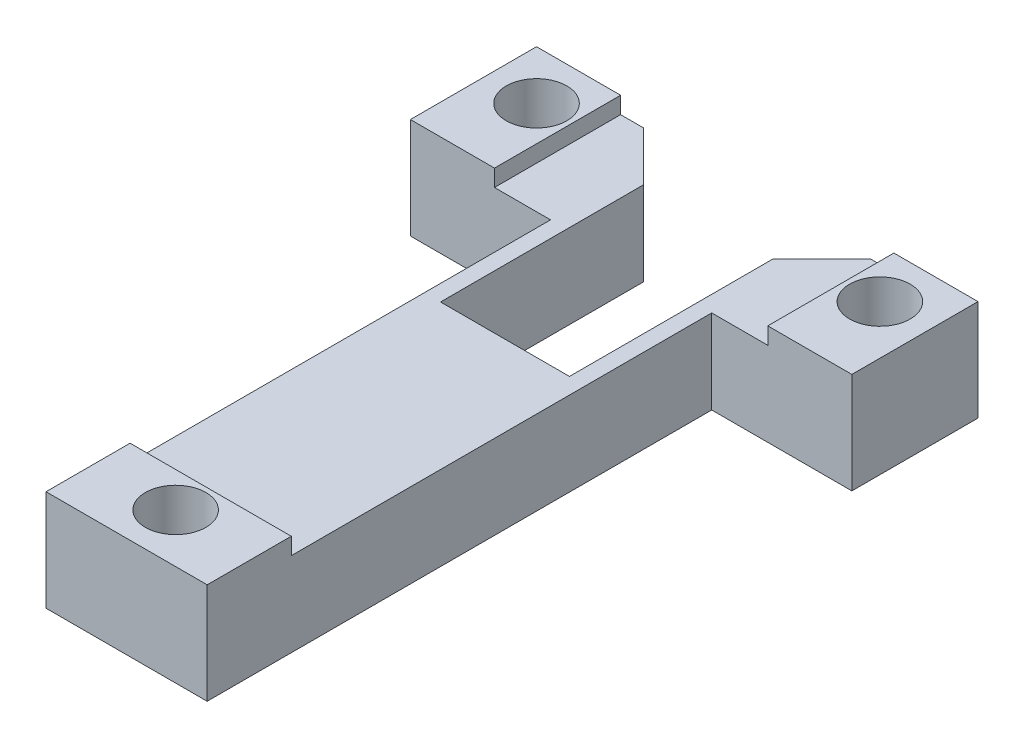
SolidWorks part; units mm, degrees
ref_plane "Front Plane" through (0, 0, 0) normal (0, 0, 1) x (1, 0, 0)
ref_plane "Top Plane" through (0, 0, 0) normal (0, 1, 0) x (1, 0, 0)
ref_plane "Right Plane" through (0, 0, 0) normal (1, 0, 0) x (0, 0, -1)
sketch "Sketch1" plane through (0, 0, 0) normal (0, 1, 0) x (1, 0, 0)
  line L0 (11.5, 45) -> (21.5, 45)
  line L1 (0, 0) -> (11.5, 0)
  line L2 (0, 0) -> (0, 45)
  line L3 (0, 45) -> (11.5, 45)
  line L4 (11.5, 0) -> (11.5, 45)
  line L5 (21.5, 45) -> (21.5, 36)
  line L6 (21.5, 36) -> (11.5, 36)
  line L7 (0, 45) -> (-10, 45)
  line L8 (-10, 45) -> (-10, 36)
  line L9 (-10, 36) -> (0, 36)
  dimension "D3" = 9
  dimension "D1" = 45
  dimension "D2" = 11.5
  dimension "D4" = 10
  dimension "D5" = 10
extrude "Boss-Extrude1" add sketch "Sketch1" along normal blind 6 contours L8 L9 L2 L7 | L6 L5 L0 L4 | L4 L3 L2 L1 region at (16.5, 0, -40.5) region at (-5, 0, -40.5)
sketch "Sketch3" plane through (0, 6, 0) normal (0, 1, 0) x (1, 0, 0)
  line L0 (-4, 45) -> (-4, 36)
  line L1 (21.5, 45) -> (-10, 45) construction
  line L2 (-10, 36) -> (0, 36) construction
  line L3 (15.5, 45) -> (15.5, 36)
  line L4 (21.5, 45) -> (-10, 45) construction
  line L5 (21.5, 36) -> (11.5, 36) construction
  line L6 (-10, 45) -> (-10, 36) construction
  line L7 (21.5, 45) -> (21.5, 36) construction
  line L8 (0, 6) -> (11.5, 6)
  line L9 (0, 0) -> (0, 36) construction
  line L10 (11.5, 0) -> (11.5, 36) construction
  line L11 (0, 0) -> (11.5, 0) construction
  line L12 (-4, 45) -> (-10, 45)
  line L14 (-10, 36) -> (-4, 36)
  line L15 (15.5, 36) -> (21.5, 36)
  line L16 (21.5, 36) -> (21.5, 45)
  line L17 (21.5, 45) -> (15.5, 45)
  line L18 (0, 6) -> (0, 0)
  line L19 (-10, 45) -> (-10, 36)
  line L20 (0, 0) -> (11.5, 0)
  line L21 (11.5, 0) -> (11.5, 6)
  dimension "D1" = 6
  dimension "D2" = 6
  dimension "D3" = 6
extrude "Boss-Extrude2" add sketch "Sketch3" along normal blind 1.2
sketch "Sketch2" plane through (0, 6, 0) normal (0, 1, 0) x (1, 0, 0)
  line L0 (5.75, 0) -> (5.75, 45) construction
  line L3 (0, 36) -> (11.5, 36) construction
  line L4 (5.75, 36) -> (5.75, 27)
  line L5 (1.15, 27) -> (10.35, 27)
  line L6 (1.15, 27) -> (1.15, 45)
  line L7 (15.5, 45) -> (-4, 45) construction
  line L8 (10.35, 27) -> (10.35, 45)
  line L9 (1.15, 45) -> (10.35, 45)
  line L10 (0, 0) -> (11.5, 0) construction
  line L11 (-10, 45) -> (-10, 36) construction
  line L12 (21.5, 45) -> (21.5, 36) construction
  line L13 (1.15, 41.5) -> (-2.35, 45)
  line L14 (10.35, 41.5) -> (13.85, 45)
  circle A0 centre (5.75, 3.5) radius 2.16
  circle A1 centre (-6.5, 41.5) radius 2.16
  circle A2 centre (18, 41.5) radius 2.16
  point P17 (5.75, 27)
  line M29 (15.5, 45) -> (-4, 45)
  dimension "D1" = 4.32
  dimension "D9" = 4.32
  dimension "D10" = 4.32
  dimension "D2" = 9
  dimension "D3" = 9.2
  dimension "D4" = 3.5
  dimension "D5" = 3.5
  dimension "D6" = 3.5
  dimension "D7" = 3.5
  dimension "D8" = 3.5
  dimension "D11" = 3.5
  dimension "D12" = 3.5
  dimension "D13" = 3.5
  dimension "D14" = 3.5
extrude "Cut-Extrude1" cut sketch "Sketch2" against normal blind 11 and the other way through all contours A0 | A2 | L9 L6 L5 L8 | A1 | L13 L6 M29 | L8 L14 M29 region at (1.3521, 6, -34.25) region at (-0.0167, 6, -43.8333) region at (11.5167, 6, -43.8333) region at (5.75, 6, -3.5) region at (-6.5, 6, -41.5) region at (18, 6, -41.5)
